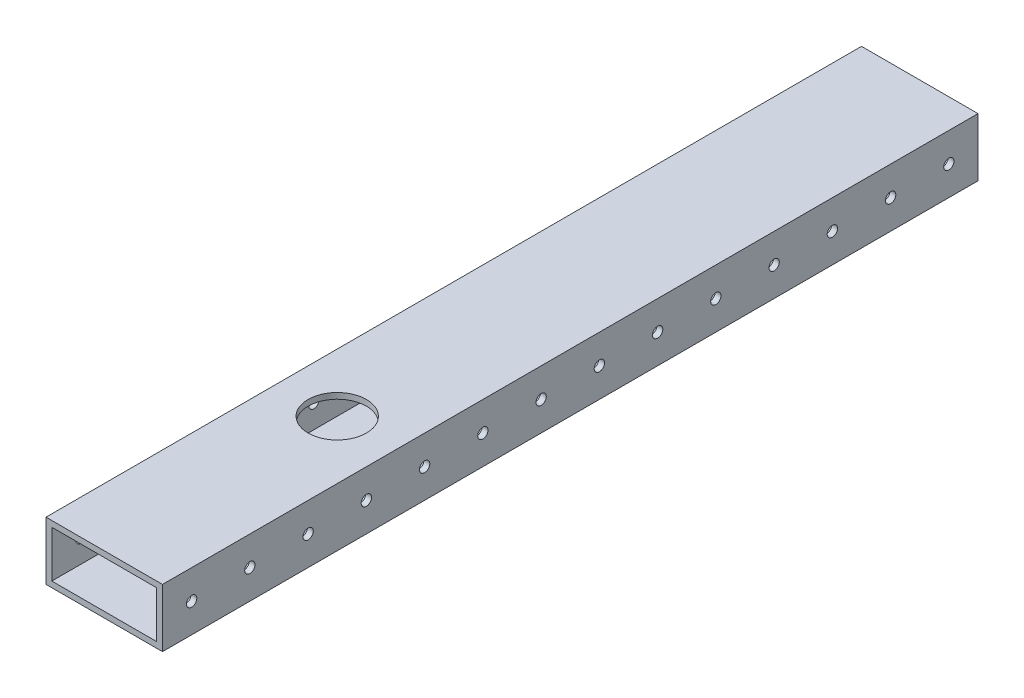
SolidWorks part; units mm, degrees
ref_plane "Front Plane" through (0, 0, 0) normal (0, 0, 1) x (1, 0, 0)
ref_plane "Top Plane" through (0, 0, 0) normal (0, 1, 0) x (1, 0, 0)
ref_plane "Right Plane" through (0, 0, 0) normal (1, 0, 0) x (0, 0, -1)
sketch "Sketch1" plane through (0, 0, 0) normal (0, 0, 1) x (1, 0, 0)
  line L1 (-25.4, -12.7) -> (25.4, -12.7)
  line L2 (-25.4, -12.7) -> (-25.4, 12.7)
  line L3 (-25.4, 12.7) -> (25.4, 12.7)
  line L4 (25.4, -12.7) -> (25.4, 12.7)
  line L5 (-25.4, -12.7) -> (25.4, 12.7) construction
  line L6 (-25.4, 12.7) -> (25.4, -12.7) construction
  line L7 (-22.86, -10.16) -> (22.86, -10.16)
  line L8 (-22.86, -10.16) -> (-22.86, 10.16)
  line L9 (-22.86, 10.16) -> (22.86, 10.16)
  line L10 (22.86, -10.16) -> (22.86, 10.16)
  line L11 (-22.86, -10.16) -> (22.86, 10.16) construction
  line L12 (-22.86, 10.16) -> (22.86, -10.16) construction
  point P0 (0, 0)
  point P6 (0, 0)
  dimension "D1" = 50.8
  dimension "D2" = 25.4
  dimension "D3" = 2.54
  dimension "D4" = 2.54
extrude "Boss-Extrude1" add sketch "Sketch1" against normal blind 355.6
hole_wizard "#8 Clearance Hole1" positions "Sketch2" profile "Sketch3" hole size "#8" standard "ANSI Inch" end condition through all
sketch "Sketch2" plane through (25.4, 0, 0) normal (1, 0, 0) x (0, 0, -1)
  line L0 (355.6, -12.7) -> (0, -12.7) construction
  point P0 (12.7, 0)
  point P16 (38.1, 0)
  point P17 (63.5, 0)
  point P18 (88.9, 0)
  point P19 (114.3, 0)
  point P20 (139.7, 0)
  point P21 (165.1, 0)
  point P22 (190.5, 0)
  point P23 (215.9, 0)
  point P24 (241.3, 0)
  point P25 (266.7, 0)
  point P26 (292.1, 0)
  point P27 (317.5, 0)
  point P28 (342.9, 0)
  dimension "D1" = 12.7
  dimension "D2" = 12.7
  dimension "D3" = 14
sketch "Sketch3" plane through (25.4, 0, -12.7) normal (0, 1, 0) x (0, 0, -1)
  line L0 (0, 0) -> (0, 50.8)
  line L1 (0, 50.8) -> (2.2479, 50.8)
  line L2 (2.2479, 50.8) -> (2.2479, 0)
  line L5 (2.2479, 0) -> (0, 0)
  line L11 (0, -6.35) -> (0, 107.95) construction
  dimension "Thru Hole Dia." = 4.4958
  dimension "Thru Hole Depth" = 50.8
hole_wizard "1 (1) Diameter Hole1" positions "Sketch6" profile "Sketch7" hole size "1" standard "ANSI Inch" end condition through all
sketch "Sketch6" plane through (0, 12.7, 0) normal (0, 1, 0) x (1, 0, 0)
  line L0 (25.4, 355.6) -> (25.4, 0) construction
  line L1 (25.4, 0) -> (-25.4, 0) construction
  point P0 (0, 101.6)
  dimension "D1" = 25.4
  dimension "D2" = 101.6
sketch "Sketch7" plane through (0, 12.7, -101.6) normal (1, 0, 0) x (0, 0, 1)
  line L0 (0, 0) -> (0, 25.4)
  line L1 (0, 25.4) -> (12.7, 25.4)
  line L2 (12.7, 25.4) -> (12.7, 0)
  line L5 (12.7, 0) -> (0, 0)
  line L11 (0, -6.35) -> (0, 107.95) construction
  dimension "Thru Hole Dia." = 25.4
  dimension "Thru Hole Depth" = 25.4
